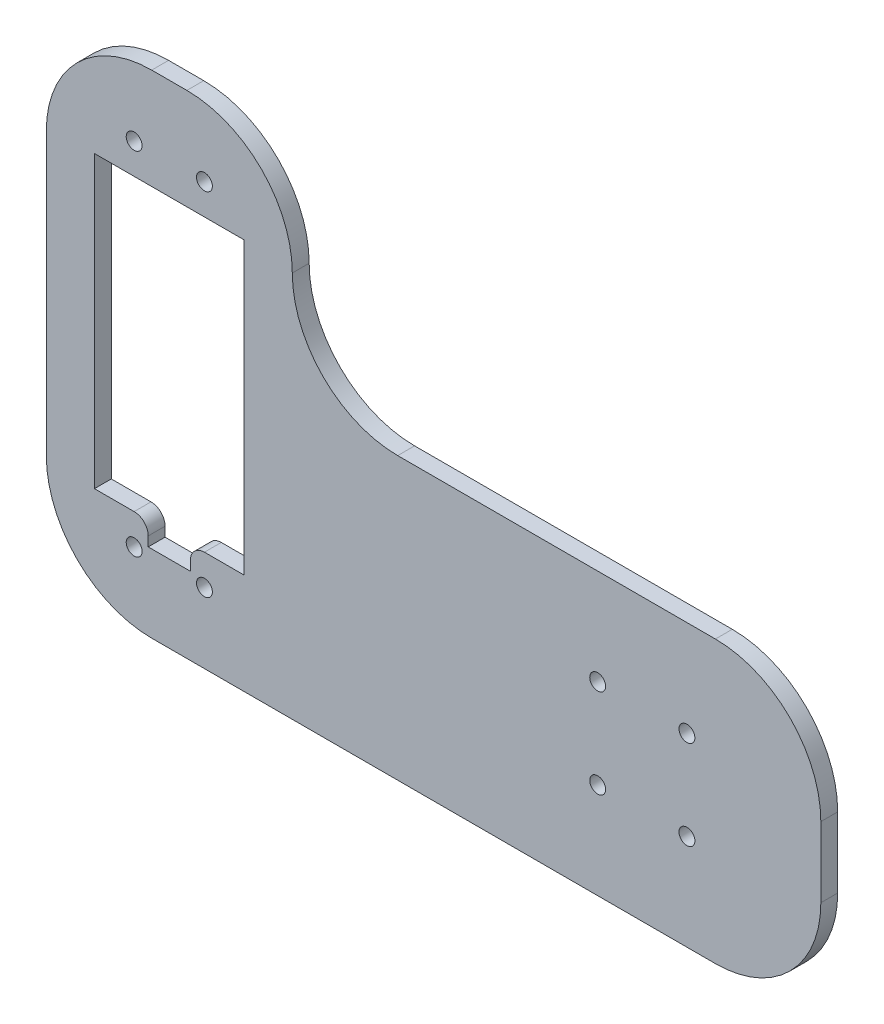
SolidWorks part; units mm, degrees
ref_plane "Front Plane" through (0, 0, 0) normal (0, 0, 1) x (1, 0, 0)
ref_plane "Top Plane" through (0, 0, 0) normal (0, 1, 0) x (1, 0, 0)
ref_plane "Right Plane" through (0, 0, 0) normal (1, 0, 0) x (0, 0, -1)
sketch "Sketch1" plane through (0, 0, 0) normal (0, 0, 1) x (1, 0, 0)
  line L0 (-96.0671, 12.0376) -> (-61.0671, 12.0376)
  line L1 (-61.0671, 12.0376) -> (-61.0671, -17.9624)
  line L2 (-61.0671, -17.9624) -> (14.1329, -17.9624)
  line L3 (14.1329, -17.9624) -> (14.1329, -57.9624)
  line L4 (14.1329, -57.9624) -> (-96.0671, -57.9624)
  line L5 (-96.0671, -57.9624) -> (-96.0671, 12.0376)
  line L6 (-78.5671, 12.0376) -> (-78.5671, -57.9624) construction
  line L7 (14.1329, -37.9624) -> (-96.0671, -37.9624) construction
  line L8 (-11.2671, -17.9624) -> (-11.2671, -57.9624) construction
  line L10 (-52.1882, -42.9624) -> (65.0745, -42.9624) construction
  line L11 (-105.5667, -2.9624) -> (-44.3168, -2.9624) construction
  line L12 (-88.5671, -2.9624) -> (-68.5671, -2.9624)
  line L13 (-88.5671, -2.9624) -> (-88.5671, -42.9624)
  line L14 (-88.5671, -42.9624) -> (-68.5671, -42.9624)
  line L15 (-68.5671, -2.9624) -> (-68.5671, -42.9624)
  circle A0 centre (-4.9171, -31.6124) radius 1.13
  circle A1 centre (-17.6171, -31.6124) radius 1.13
  circle A2 centre (-17.6171, -44.3124) radius 1.13
  circle A3 centre (-4.9171, -44.3124) radius 1.13
  circle A4 centre (-73.5671, 2.0376) radius 1.13
  circle A5 centre (-73.5671, -47.9624) radius 1.13
  circle A6 centre (-83.5671, 2.0376) radius 1.13
  circle A7 centre (-83.5671, -47.9624) radius 1.13
  dimension "D9" = 25.4
  dimension "D10" = 2.26
  dimension "D15" = 2.26
  dimension "D20" = 2.26
  dimension "D1" = 35
  dimension "D2" = 40
  dimension "D3" = 70
  dimension "D4" = 75.2
  dimension "D5" = 15
  dimension "D6" = 15
  dimension "D7" = 20
  dimension "D8" = 10
  dimension "D11" = 6.35
  dimension "D12" = 6.35
  dimension "D16" = 5
  dimension "D17" = 5
  dimension "D18" = 5
  dimension "D19" = 5
extrude "Boss-Extrude1" add sketch "Sketch1" along normal blind 2.4
sketch "Sketch2" plane through (0, 0, 2.4) normal (0, 0, 1) x (1, 0, 0)
  line L0 (-78.5671, 12.0376) -> (-78.5671, -57.9624) construction
  line L1 (-61.0671, 12.0376) -> (-96.0671, 12.0376) construction
  line L2 (-96.0671, -57.9624) -> (14.1329, -57.9624) construction
  line L3 (-88.5671, -42.9624) -> (-68.5671, -42.9624) construction
  line L4 (-81.5671, -42.9624) -> (-75.5671, -42.9624)
  line L5 (-81.5671, -42.9624) -> (-81.5671, -46.9624)
  line L6 (-81.5671, -46.9624) -> (-75.5671, -46.9624)
  line L7 (-75.5671, -42.9624) -> (-75.5671, -46.9624)
  dimension "D1" = 4
  dimension "D2" = 6
  dimension "D3" = 3
extrude "Cut-Extrude1" cut sketch "Sketch2" against normal blind 2.4
sketch "Sketch3" plane through (0, 0, 2.4) normal (0, 0, 1) x (1, 0, 0)
  line L0 (-89.2171, -2.3124) -> (-67.9171, -2.3124)
  line L1 (-88.5671, -2.9624) -> (-68.5671, -2.9624)
  line L2 (-88.5671, -2.9624) -> (-88.5671, -42.9624)
  line L3 (-88.5671, -42.9624) -> (-68.5671, -42.9624)
  line L4 (-68.5671, -2.9624) -> (-68.5671, -42.9624)
  line L5 (-67.9171, -2.3124) -> (-67.9171, -43.6124)
  line L6 (-89.2171, -43.6124) -> (-67.9171, -43.6124)
  line L7 (-89.2171, -2.3124) -> (-89.2171, -43.6124)
  dimension "D1" = 0.65
extrude "Cut-Extrude2" cut sketch "Sketch3" against normal blind 2.4
fillet "Fillet1" radius 2 2 edges at (-75.5671, -43.6124, 1.2) (-81.5671, -43.6124, 1.2)
fillet "Fillet2" radius 15 6 edges at (-61.0671, -17.9624, 1.2) (14.1329, -17.9624, 1.2) (14.1329, -57.9624, 1.2) (-96.0671, -57.9624, 1.2) (-61.0671, 12.0376, 1.2) (-96.0671, 12.0376, 1.2)
